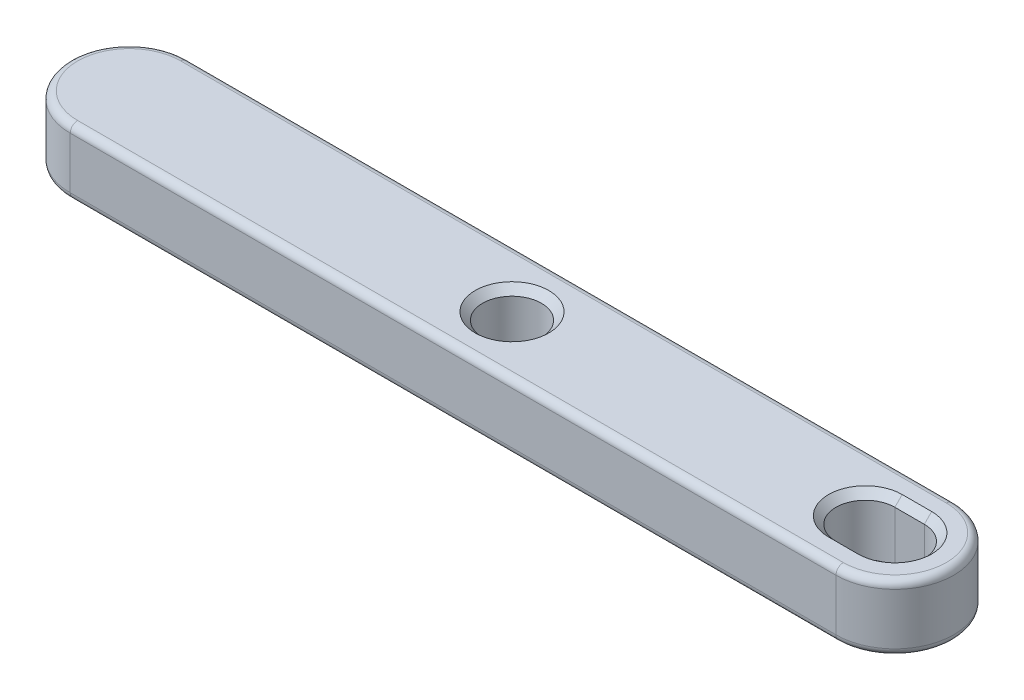
SolidWorks part; units mm, degrees
material "Aço cromo inoxidável"
ref_plane "Plano frontal" through (0, 0, 0) normal (0, 0, 1) x (1, 0, 0)
ref_plane "Plano superior" through (0, 0, 0) normal (0, 1, 0) x (1, 0, 0)
ref_plane "Plano direito" through (0, 0, 0) normal (1, 0, 0) x (0, 0, -1)
sketch "Esboço1" plane through (0, 0, 0) normal (0, 1, 0) x (1, 0, 0)
  line L0 (-26, 0) -> (26, 0) construction
  line L1 (-26, 4) -> (26, 4)
  line L2 (-26, -4) -> (26, -4)
  line L3 (26, 0) -> (24, 0) construction
  line L4 (26, -2) -> (24, -2)
  line L5 (26, 2) -> (24, 2)
  arc A0 (-26, 4) -> (-26, -4) centre (-26, 0) ccw
  arc A1 (26, -4) -> (26, 4) centre (26, 0) ccw
  circle A2 centre (0, 0) radius 2
  arc A3 (26, -2) -> (26, 2) centre (26, 0) ccw
  arc A4 (24, 2) -> (24, -2) centre (24, 0) ccw
  point P2 (0, 0)
  point P12 (25, 0)
  dimension "D3" = 4
  dimension "D1" = 8
  dimension "D2" = 60
  dimension "D4" = 4
  dimension "D5" = 6
extrude "Ressalto-extrusão1" add sketch "Esboço1" along normal mid plane 4.5
chamfer "Chanfro1" distance 0.5 angle 45 10 edges at (28, -2.25, 0) (25, -2.25, -2) (25, -2.25, 2) (22, -2.25, 0) (0, -2.25, 2) (25, 2.25, 2) (28, 2.25, 0) (22, 2.25, 0) (25, 2.25, -2) (0, 2.25, 2)
fillet "Filete1" radius 0.5 8 edges at (-30, 2.25, 0) (0, 2.25, -4) (30, 2.25, 0) (-30, -2.25, 0) (0, -2.25, -4) (30, -2.25, 0) (0, 2.25, 4) (0, -2.25, 4)
